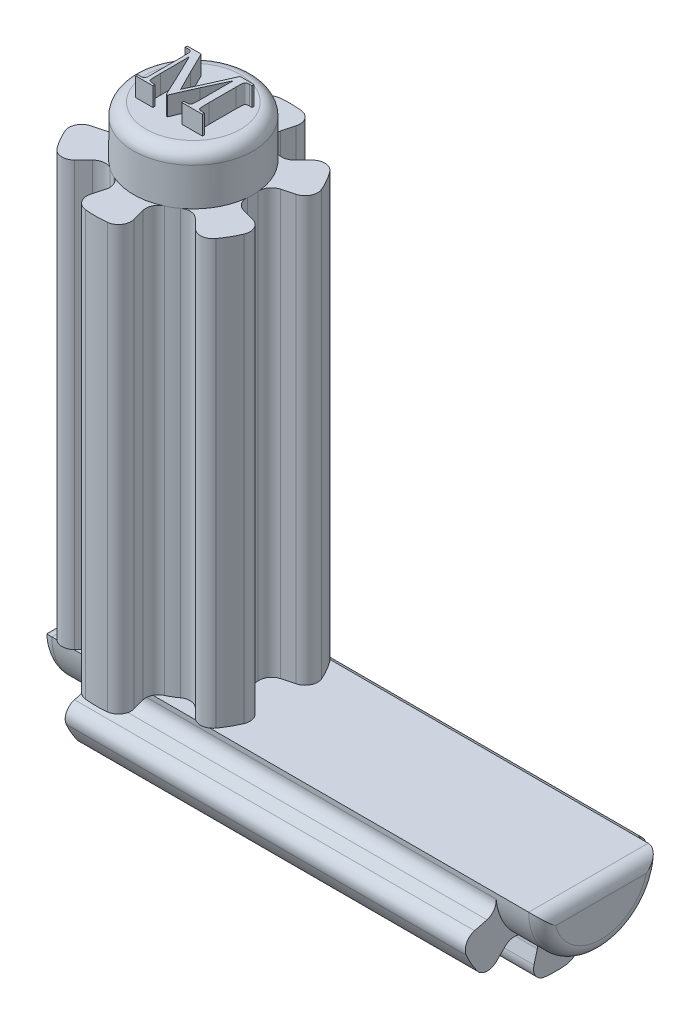
SolidWorks part; units mm, degrees
ref_plane "Front Plane" through (0, 0, 0) normal (0, 0, 1) x (1, 0, 0)
ref_plane "Top Plane" through (0, 0, 0) normal (0, 1, 0) x (1, 0, 0)
ref_plane "Right Plane" through (0, 0, 0) normal (1, 0, 0) x (0, 0, -1)
sketch "Sketch1" plane through (0, 0, 0) normal (0, 1, 0) x (1, 0, 0)
  line L3 (-1.6794, 1.6794) -> (-2.74, 2.74)
  line L5 (-1.6794, -1.6794) -> (-2.74, -2.74)
  line L8 (0.6147, -2.2941) -> (1.0029, -3.743)
  line L9 (-0.6147, -2.2941) -> (-1.0029, -3.743)
  line L11 (-0.6147, 2.2941) -> (-1.0029, 3.743)
  line L12 (0.6147, 2.2941) -> (1.0029, 3.743)
  line L15 (-2.2941, 0.6147) -> (-3.743, 1.0029)
  line L16 (-2.2941, -0.6147) -> (-3.743, -1.0029)
  line L18 (1.7174, -1.6405) -> (2.7779, -2.7017)
  line L19 (2.2941, -0.6147) -> (3.743, -1.0029)
  line L20 (2.2941, 0.6147) -> (3.743, 1.0029)
  line L21 (1.6794, 1.6794) -> (2.74, 2.74)
  arc A0 (-2.74, 2.74) -> (-3.743, 1.0029) centre (0, 0) ccw
  arc A1 (-0.6147, 2.2941) -> (-1.6794, 1.6794) centre (0, 0) ccw
  arc A2 (0.6147, -2.2941) -> (1.7174, -1.6405) centre (0, 0) ccw
  arc A3 (-2.2941, 0.6147) -> (-2.2941, -0.6147) centre (0, 0) ccw
  arc A4 (-1.6794, -1.6794) -> (-0.6147, -2.2941) centre (0, 0) ccw
  arc A5 (2.2941, -0.6147) -> (2.2941, 0.6147) centre (0, 0) ccw
  arc A6 (1.6794, 1.6794) -> (0.6147, 2.2941) centre (0, 0) ccw
  arc A7 (1.0029, 3.743) -> (-1.0029, 3.743) centre (0, 0) ccw
  arc A8 (3.743, 1.0029) -> (2.74, 2.74) centre (0, 0) ccw
  arc A9 (2.7779, -2.7017) -> (3.743, -1.0029) centre (0, 0) ccw
  arc A10 (-1.0029, -3.743) -> (1.0029, -3.743) centre (0, 0) ccw
  arc A11 (-3.743, -1.0029) -> (-2.74, -2.74) centre (0, 0) ccw
  dimension "D2" = 3.875
  dimension "D3" = 2.375
  dimension "D10" = 30
  dimension "D11" = 30
  dimension "D14" = 30
  dimension "D15" = 30
extrude "Boss-Extrude1" add sketch "Sketch1" along normal blind 16.85
sketch "Sketch2" plane through (0, 16.85, 0) normal (0, 1, 0) x (1, 0, 0)
  circle A0 centre (0, 0) radius 2.38
extrude "Boss-Extrude2" add sketch "Sketch2" along normal blind 2
ref_plane "Plane5" through (13.9, 0, 0) normal (1, 0, 0) x (0, 0, -1)
sketch "Sketch10" plane through (13.9, 0, 0) normal (1, 0, 0) x (0, 0, -1)
  line L0 (-2.375, 0) -> (2.375, 0)
  line L1 (-2.2941, -0.6147) -> (-3.743, -1.0029)
  line L2 (2.2941, -0.6147) -> (3.743, -1.0029)
  line L3 (-1.6794, -1.6794) -> (-2.74, -2.74)
  line L4 (1.6794, -1.6794) -> (2.74, -2.74)
  line L5 (-0.6147, -2.2941) -> (-1.0029, -3.743)
  line L6 (0.6147, -2.2941) -> (1.0029, -3.743)
  arc A0 (-3.743, -1.0029) -> (-2.74, -2.74) centre (0, 0) ccw
  arc A1 (-2.375, 0) -> (-2.2941, -0.6147) centre (0, 0) ccw
  arc A2 (2.2941, -0.6147) -> (2.375, 0) centre (0, 0) ccw
  arc A3 (0.6147, -2.2941) -> (1.6794, -1.6794) centre (0, 0) ccw
  arc A4 (-1.6794, -1.6794) -> (-0.6147, -2.2941) centre (0, 0) ccw
  arc A5 (-1.0029, -3.743) -> (1.0029, -3.743) centre (0, 0) ccw
  arc A6 (2.74, -2.74) -> (3.743, -1.0029) centre (0, 0) ccw
  arc A7 (-2.375, 0) -> (2.375, 0) centre (0, 0) ccw
  dimension "D1" = 3.875
  dimension "D2" = 2.375
  dimension "D5" = 15
  dimension "D6" = 15
  dimension "D7" = 30
  dimension "D8" = 30
extrude "Boss-Extrude9" add sketch "Sketch10" against normal blind 19.95 from offset 2.3 contours A1 A7 A4 A3 A2 L0 region at (13.9, -1.008, 0)
extrude "Boss-Extrude10" add sketch "Sketch10<3>" against normal blind 15.9 from offset 0.5 contours A7 L4 A6 L2 | A7 L5 A5 L6 | A7 L1 A0 L3 region at (13.9, -1.5744, 2.7269) region at (13.9, -1.5744, -2.7269) region at (13.9, -3.1487, 0)
sketch "Sketch10<3>" plane through (13.9, 0, 0) normal (1, 0, 0) x (0, 0, -1) same geometry as "Sketch10"
sketch "Sketch11" plane through (0, 18.85, 0) normal (0, 1, 0) x (1, 0, 0)
  text T0 "M" font "Book Antiqua" height in points 8
fillet "Fillet2" radius 0.5 39 edges at (16.2, 0, 0) (16.2, -2.375, 0) (0, 18.85, 2.38) (1.6794, 8.425, -1.6794) (2.74, 8.425, -2.74) (3.743, 8.425, -1.0029) (2.2941, 8.425, -0.6147) (2.2941, 8.425, 0.6147) (3.743, 8.425, 1.0029) (2.7779, 8.425, 2.7017) (1.7174, 8.425, 1.6405) (0.6147, 8.425, 2.2941) (1.0029, 8.425, 3.743) (-1.0029, 8.425, 3.743) (-0.6147, 8.425, 2.2941) (-1.6794, 8.425, 1.6794) (-2.74, 8.425, 2.74) (-3.743, 8.425, 1.0029) (-2.2941, 8.425, 0.6147) (-2.2941, 8.425, -0.6147) (-3.743, 8.425, -1.0029) (-2.74, 8.425, -2.74) (-1.6794, 8.425, -1.6794) (-0.6147, 8.425, -2.2941) (-1.0029, 8.425, -3.743) (0.6147, 8.425, -2.2941) (1.0029, 8.425, -3.743) (6.45, -0.6147, -2.2941) (6.45, -1.0029, -3.743) (6.45, -2.74, -2.74) (6.45, -1.6794, -1.6794) (6.45, -2.2941, -0.6147) (6.45, -3.743, -1.0029) (6.45, -3.743, 1.0029) (6.45, -2.2941, 0.6147) (6.45, -1.6794, 1.6794) (6.45, -2.74, 2.74) (6.45, -1.0029, 3.743) (6.45, -0.6147, 2.2941)
fillet "Fillet3" radius 0.5 2 edges at (-3.75, -2.375, 0) (-3.75, 0, 0)
extrude "Boss-Extrude11" add sketch "Sketch11" along normal mid plane 1.5
